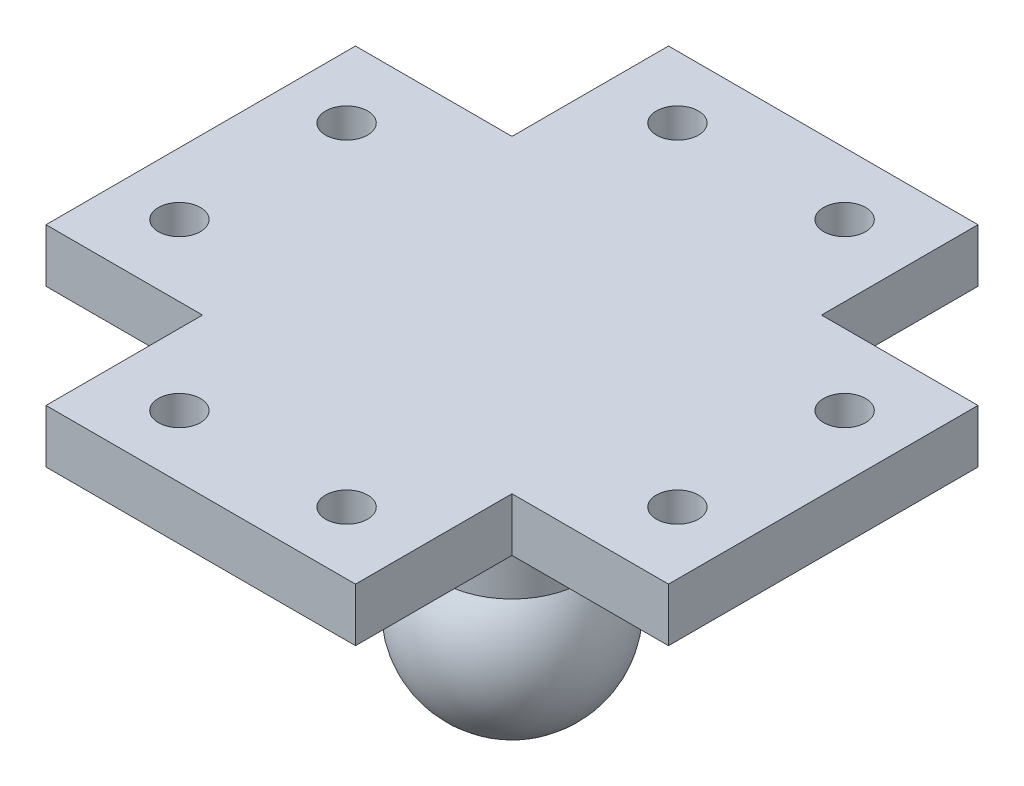
SolidWorks part; units mm, degrees
ref_plane "Front Plane" through (0, 0, 0) normal (0, 0, 1) x (1, 0, 0)
ref_plane "Top Plane" through (0, 0, 0) normal (0, 1, 0) x (1, 0, 0)
ref_plane "Right Plane" through (0, 0, 0) normal (1, 0, 0) x (0, 0, -1)
sketch "Sketch1" plane through (0, 0, 0) normal (0, 0, 1) x (1, 0, 0)
  line L0 (0, -6.604) -> (0, 6.604)
  line L1 (0, 6.604) -> (0, 14.3798)
  line L2 (-5.08, 14.3798) -> (0, 14.3798)
  line L3 (-5.08, 14.3798) -> (-5.08, 4.2198)
  arc A1 (-5.08, 4.2198) -> (0, -6.604) centre (0, 0) ccw
  point P5 (0, 9.2998)
  dimension "D1" = 6.604
  dimension "D2" = 5.08
  dimension "D3" = 10.16
revolve "Revolve3" add sketch "Sketch1" angle 360 about L0 region at (-2.7448, 3.9059, 0)
sketch "Sketch2" plane through (0, 14.3798, 0) normal (0, 1, 0) x (1, 0, 0)
  line L1 (-22.225, 11.049) -> (22.225, 11.049)
  line L2 (-22.225, 11.049) -> (-22.225, -11.049)
  line L3 (-22.225, -11.049) -> (22.225, -11.049)
  line L4 (22.225, 11.049) -> (22.225, -11.049)
  line L5 (-22.225, 11.049) -> (22.225, -11.049) construction
  line L6 (-22.225, -11.049) -> (22.225, 11.049) construction
  line L7 (11.049, -22.225) -> (-11.049, -22.225)
  line L8 (11.049, -22.225) -> (11.049, 22.225)
  line L9 (11.049, 22.225) -> (-11.049, 22.225)
  line L10 (-11.049, -22.225) -> (-11.049, 22.225)
  line L11 (11.049, -22.225) -> (-11.049, 22.225) construction
  line L12 (11.049, 22.225) -> (-11.049, -22.225) construction
  circle A0 centre (-17.78, -5.969) radius 1.5
  circle A1 centre (-17.78, 5.969) radius 1.5
  circle A2 centre (-5.969, 17.78) radius 1.5
  circle A3 centre (5.969, 17.78) radius 1.5
  circle A4 centre (17.78, 5.969) radius 1.5
  circle A5 centre (17.78, -5.969) radius 1.5
  circle A6 centre (5.969, -17.78) radius 1.5
  circle A7 centre (-5.969, -17.78) radius 1.5
  point P0 (0, 0)
  point P6 (0, 0)
  point P30 (0, 0)
  circle M9 centre (0, 0) radius 5.08
  dimension "D3" = 3
  dimension "D1" = 22.098
  dimension "D2" = 44.45
  dimension "D4" = 5.08
  dimension "D5" = 5.08
  dimension "D6" = 4.445
  dimension "D8" = 6.731
  dimension "D7" = 4
extrude "Boss-Extrude1" add sketch "Sketch2" along normal blind 3.81 contours L3 L10 L1 L2 | L10 L1 M9 | M9 | L10 L3 M9 | L10 L7 L8 L3 | L8 L3 L4 L1 | L8 L1 M9 | L3 L8 M9 | L10 L1 L8 L9 region at (-16.5676, 14.3798, 0) region at (0, 14.3798, -16.5676) region at (0, 14.3798, -10.7365) region at (16.5676, 14.3798, 0) region at (0, 14.3798, 16.5676) region at (0, 14.3798, 0)
fillet "Fillet1" radius 5.08 1 edges at (0, 14.3798, -5.08)
ref_plane "Plane1" through (0, 4.2198, 0) normal (0, 1, 0) x (1, 0, 0)
sketch "Sketch3" plane through (0, 4.2198, 0) normal (0, 1, 0) x (1, 0, 0)
  point P0 (0, 0)
